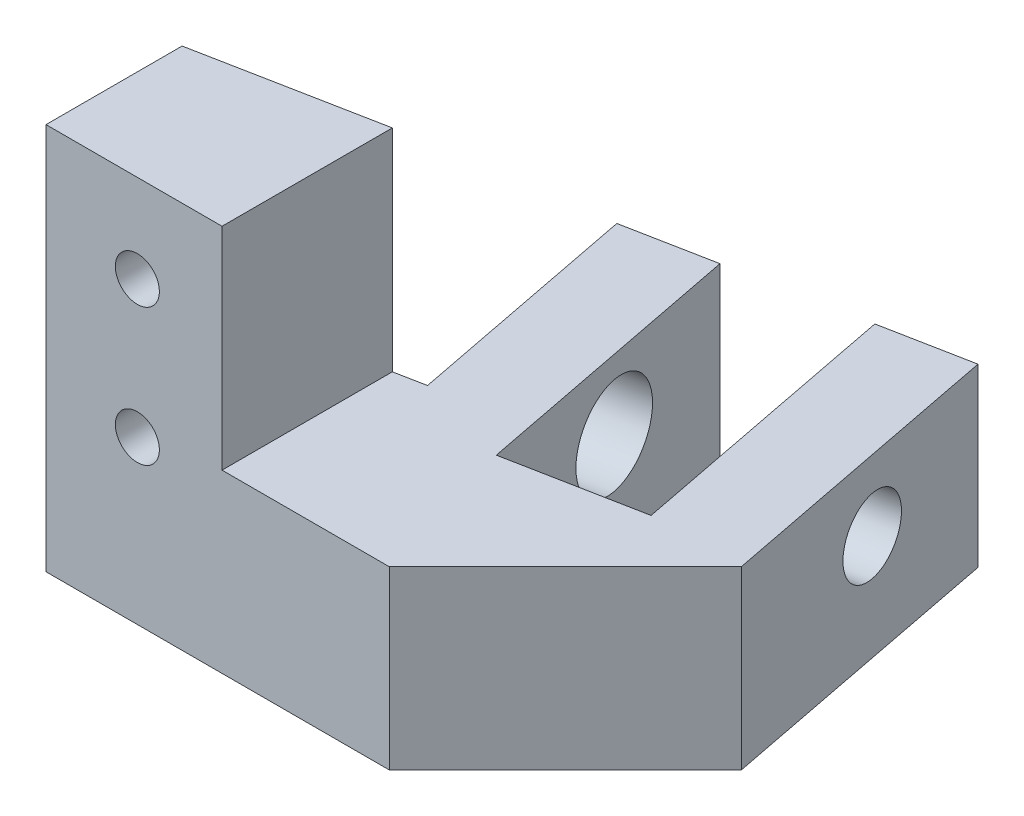
SolidWorks part; units mm, degrees
ref_plane "Plan de face" through (0, 0, 0) normal (0, 0, 1) x (1, 0, 0)
ref_plane "Plan de dessus" through (0, 0, 0) normal (0, 1, 0) x (1, 0, 0)
ref_plane "Plan de droite" through (0, 0, 0) normal (1, 0, 0) x (0, 0, -1)
sketch "Esquisse1" plane through (0, 0, 0) normal (0, 0, 1) x (1, 0, 0)
  line L0 (0, 0) -> (29.5, 0)
  line L1 (29.5, 0) -> (29.5, 10)
  line L2 (29.5, 10) -> (10, 10)
  line L3 (10, 10) -> (10, 22)
  line L4 (10, 22) -> (0, 22)
  line L5 (0, 22) -> (0, 0)
  dimension "D1" = 10
  dimension "D2" = 22
  dimension "D3" = 10
  dimension "D4" = 19.5
extrude "Boss.-Extru.1" add sketch "Esquisse1" along normal blind 10
sketch "Esquisse2" plane through (0, 10, 0) normal (0, 1, 0) x (1, 0, 0)
  line L0 (29.5, 0) -> (26.2562, 16.6877)
  line L1 (26.2562, 16.6877) -> (21.3481, 15.7336)
  line L2 (21.3481, 15.7336) -> (24.4064, 0)
  line L3 (29.5, 0) -> (10, 0) construction
  line L4 (24.4064, 0) -> (29.5, 0)
  line L5 (16.766, 0) -> (13.9859, 14.3025)
  line L6 (13.9859, 14.3025) -> (9.0778, 13.3485)
  line L7 (9.0778, 13.3485) -> (11.6725, 0)
  line L8 (16.766, 0) -> (11.6725, 0)
  line L9 (29.5, -10) -> (29.5, 0) construction
  dimension "D1" = 5
  dimension "D2" = 7.5
  dimension "D3" = 191
  dimension "D4" = 17
extrude "Boss.-Extru.2" add sketch "Esquisse2" against normal up to surface (10 mm away) up to face at (14.75, 0, 5)
sketch "Esquisse3" plane through (0, 10, 0) normal (0, 1, 0) x (1, 0, 0)
  line L0 (16.766, 0) -> (17.0523, -1.4724)
  line L1 (17.0523, -1.4724) -> (24.4145, -0.0414)
  line L2 (24.4145, -0.0414) -> (24.4064, 0)
  line L3 (21.3481, 15.7336) -> (24.4064, 0) construction
  line L4 (16.766, 0) -> (13.9859, 14.3025) construction
  line L5 (24.4064, 0) -> (16.766, 0)
  dimension "D1" = 1.5
extrude "Enlèv. mat.-Extru.1" cut sketch "Esquisse3" against normal up to next
sketch "Esquisse4" plane through (11.2475, 0, -2.1863) normal (-0.9816, 0, 0.1908) x (0.1908, 0, 0.9816)
  line L0 (-11.3711, 10) -> (2.2272, 10) construction
  line L1 (2.2272, 0) -> (2.2272, 10) construction
  circle A0 centre (-3.7728, 6) radius 2.75
  dimension "D2" = 5.5
  dimension "D1" = 4
  dimension "D3" = 6
extrude "Enlèv. mat.-Extru.2" cut sketch "Esquisse4" against normal up to next
sketch "Esquisse5" plane through (23.5178, 0, -4.5714) normal (-0.9816, 0, 0.1908) x (0.1908, 0, 0.9816)
  circle A0 centre (-3.7728, 6) radius 2.1
  circle A1 centre (-3.7728, 6) radius 2.75 construction
  circle A2 centre (-3.7728, 6) radius 2.75 construction
  dimension "D1" = 4.2
extrude "Enlèv. mat.-Extru.3" cut sketch "Esquisse5" against normal up to next
chamfer "Chanfrein1" distance 10 angle 45 1 edges at (29.5, 5, 10)
sketch "Esquisse6" plane through (0, 22, 0) normal (0, 1, 0) x (1, 0, 0)
  line L0 (0, 0) -> (11.6725, 0)
  line L1 (11.6725, 0) -> (0, -2.2689)
  line L2 (0, -10) -> (0, 0) construction
  line L3 (0, -2.2689) -> (0, 0)
  line L4 (9.0778, 13.3485) -> (11.6725, 0) construction
extrude "Enlèv. mat.-Extru.4" cut sketch "Esquisse6" against normal up to next
sketch "Esquisse7" plane through (0, 0, 10) normal (0, 0, 1) x (1, 0, 0)
  line L0 (0, 22) -> (0, 0) construction
  line L1 (10, 22) -> (0, 22) construction
  circle A0 centre (5.19, 17) radius 1.25
  circle A1 centre (5.19, 9.22) radius 1.25
  dimension "D1" = 2.5
  dimension "D2" = 5.19
  dimension "D3" = 5
  dimension "D4" = 7.78
extrude "Enlèv. mat.-Extru.5" cut sketch "Esquisse7" against normal up to next
